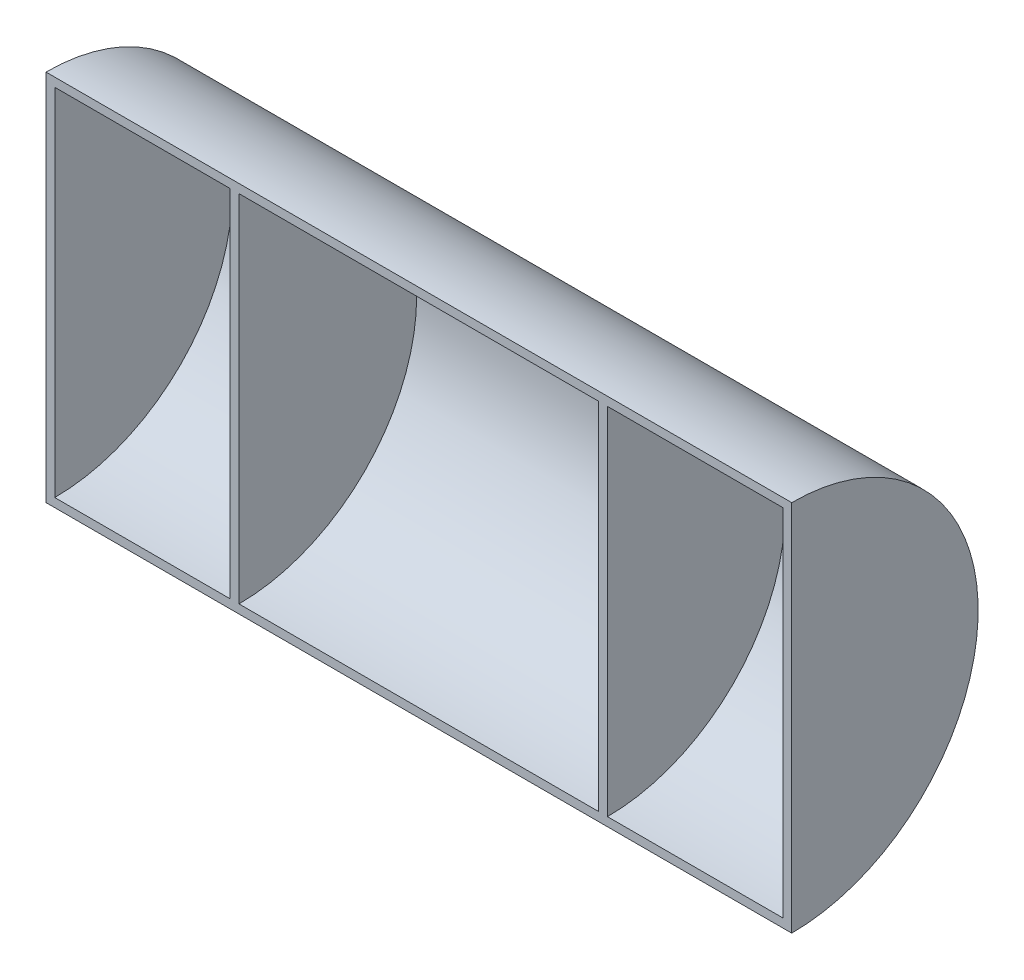
SolidWorks part; units mm, degrees
ref_plane "Front Plane" through (0, 0, 0) normal (0, 0, 1) x (1, 0, 0)
ref_plane "Top Plane" through (0, 0, 0) normal (0, 1, 0) x (1, 0, 0)
ref_plane "Right Plane" through (0, 0, 0) normal (1, 0, 0) x (0, 0, -1)
sketch "Profile Sketch" plane through (0, 0, 0) normal (1, 0, 0) x (0, 0, -1)
  line L0 (0, 42.5) -> (0, -42.5)
  arc A0 (0, -42.5) -> (0, 42.5) centre (0, 0) ccw
  dimension "D1" = 85
extrude "Profile Extrude" add sketch "Profile Sketch" against normal blind 170
shell "Profile Shell" thickness 2 removed face at (-85, 0, 0)
sketch "Support Sketch" plane through (0, 0, 0) normal (0, 0, 1) x (1, 0, 0)
  line L0 (-168, 40.5) -> (-2, 40.5) construction
  line L1 (-168, -40.5) -> (-2, -40.5) construction
  line L2 (-128, 40.5) -> (-126, 40.5)
  line L3 (-128, 40.5) -> (-128, -40.5)
  line L4 (-128, -40.5) -> (-126, -40.5)
  line L5 (-126, 40.5) -> (-126, -40.5)
  line L6 (-128, 40.5) -> (-126, -40.5) construction
  line L7 (-128, -40.5) -> (-126, 40.5) construction
  line L8 (-168, -40.5) -> (-168, 40.5) construction
  line L9 (-44, 40.5) -> (-42, 40.5)
  line L10 (-44, 40.5) -> (-44, -40.5)
  line L11 (-44, -40.5) -> (-42, -40.5)
  line L12 (-42, 40.5) -> (-42, -40.5)
  line L13 (-44, 40.5) -> (-42, -40.5) construction
  line L14 (-44, -40.5) -> (-42, 40.5) construction
  line L15 (-2, 40.5) -> (-2, -40.5) construction
  point P1 (-127, 0)
  point P7 (-43, 0)
  dimension "D1" = 2
  dimension "D2" = 2
  dimension "D3" = 40
  dimension "D4" = 40
extrude "Support Extrude" add sketch "Support Sketch" against normal up to surface up to face at (-85, 0, -20.25)
sketch "Angle Sketch" plane through (0, 0, 0) normal (1, 0, 0) x (0, 0, -1)
  line L0 (0, 0) -> (42.5, 0) construction
  arc A0 (0, -42.5) -> (0, 42.5) centre (0, 0) ccw construction
  point P7 (42.5, 0)
